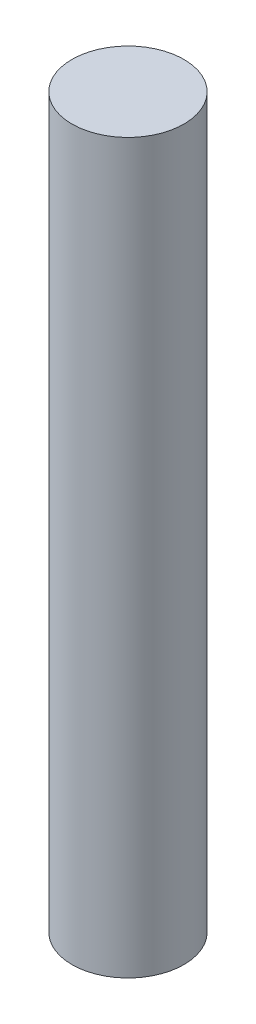
SolidWorks part; units mm, degrees
material "Plain Carbon Steel"
ref_plane "Front Plane" through (0, 0, 0) normal (0, 0, 1) x (1, 0, 0)
ref_plane "Top Plane" through (0, 0, 0) normal (0, 1, 0) x (1, 0, 0)
ref_plane "Right Plane" through (0, 0, 0) normal (1, 0, 0) x (0, 0, -1)
sketch "Sketch1" plane through (0, 0, 0) normal (0, 1, 0) x (1, 0, 0)
  circle A0 centre (0, 0) radius 3.175
  dimension "D1" = 6.35
extrude "Boss-Extrude1" add sketch "Sketch1" along normal blind 41.275
